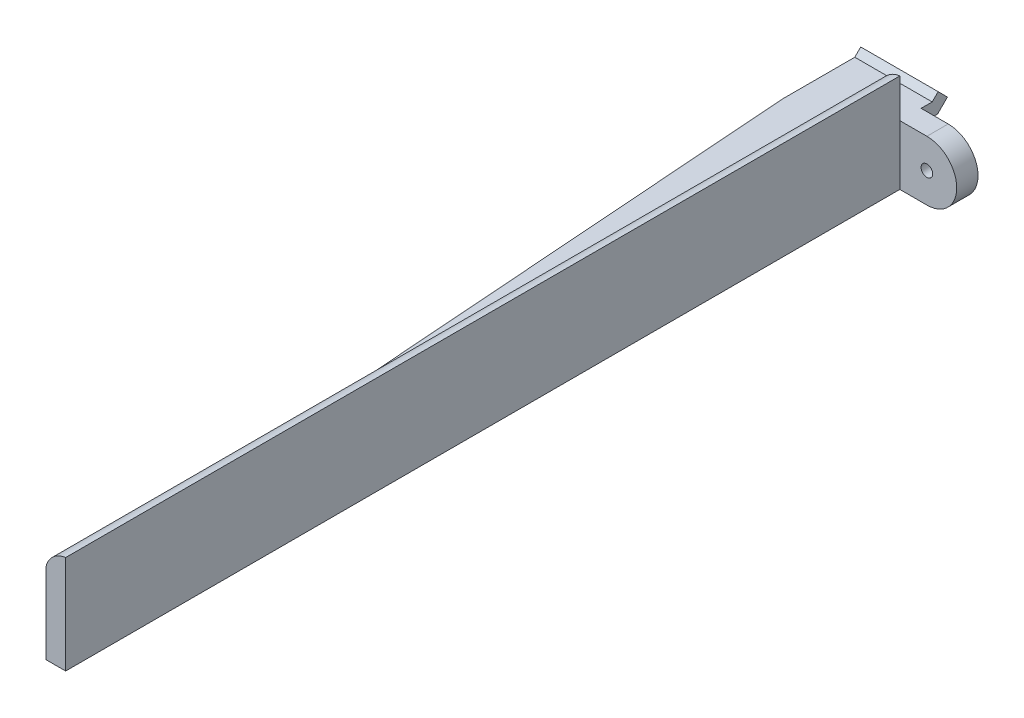
SolidWorks part; units mm, degrees
ref_plane "Front Plane" through (0, 0, 0) normal (0, 0, 1) x (1, 0, 0)
ref_plane "Top Plane" through (0, 0, 0) normal (0, 1, 0) x (1, 0, 0)
ref_plane "Right Plane" through (0, 0, 0) normal (1, 0, 0) x (0, 0, -1)
sketch "Sketch2" plane through (0, 0, 0) normal (0, 0, 1) x (1, 0, 0)
  line L0 (0, 5.9203) -> (0, 8.9503) construction
  line L1 (-5, -5.8182) -> (5, -5.8182)
  line L2 (-5, -5.8182) -> (-5, 8.9503)
  line L3 (-5, 8.9503) -> (5, 8.9503)
  line L4 (5, -5.8182) -> (5, 8.9503)
  line L5 (97.4, 8.9503) -> (117.4, 8.9503) construction
  line L7 (41.5859, 5.9203) -> (-10.4141, 5.9203) construction
  line L8 (0, -5.8182) -> (0, -2.7882) construction
  point P0 (0, 0)
  dimension "D1" = 10
extrude "Boss-Extrude1" add sketch "Sketch2" along normal blind 5
sketch "Sketch8" plane through (-5, 0, 0) normal (-1, 0, 0) x (0, 0, 1)
  line L6 (-0.15, 5.7703) -> (0, 5.7703)
  line L7 (0, 8.9503) -> (0, -5.8182) construction
  line L8 (0, 5.7703) -> (0, 4.0703)
  line L9 (0, 4.0703) -> (-0.15, 4.0703)
  line L11 (-0.15, -1.9297) -> (0, -1.9297)
  line L12 (-2.1379, 4.0703) -> (-0.15, 4.0703)
  line L13 (-0.15, 4.0703) -> (-0.15, 5.7703)
  line L14 (-0.15, 5.7703) -> (-1.4337, 5.7703)
  line L15 (-1.4337, 5.7703) -> (-2.2, 6.5366)
  line L16 (-2.2, 6.5366) -> (-3.4021, 5.3345)
  line L17 (-3.4021, 5.3345) -> (-2.1379, 4.0703)
  line L18 (-2.1379, 4.0703) -> (-0.15, 4.0703)
  line L20 (-0.15, 5.7703) -> (-1.4337, 5.7703)
  line L21 (-1.4337, 5.7703) -> (-2.2, 6.5366)
  line L22 (-2.2, 6.5366) -> (-3.4021, 5.3345)
  line L23 (-3.4021, 5.3345) -> (-2.1379, 4.0703)
  line L24 (-2.1379, -1.9297) -> (-0.15, -1.9297)
  line L25 (-0.15, -1.9297) -> (-0.15, -0.2297)
  line L26 (-0.15, -0.2297) -> (-1.4337, -0.2297)
  line L27 (-1.4337, -0.2297) -> (-2.2, 0.5366)
  line L28 (-2.2, 0.5366) -> (-3.4021, -0.6655)
  line L29 (-3.4021, -0.6655) -> (-2.1379, -1.9297)
  line L30 (-2.1379, -1.9297) -> (-0.15, -1.9297)
  line L32 (-0.15, -0.2297) -> (-1.4337, -0.2297)
  line L33 (-1.4337, -0.2297) -> (-2.2, 0.5366)
  line L34 (-2.2, 0.5366) -> (-3.4021, -0.6655)
  line L35 (-3.4021, -0.6655) -> (-2.1379, -1.9297)
  line L37 (-0.15, -0.2297) -> (0, -0.2297)
  line L38 (0, -1.9297) -> (0, -0.2297)
  dimension "D1" = 0.15
  dimension "D2" = 0.15
extrude "Boss-Extrude4" add sketch "Sketch8" against normal up to surface (10 mm away) up to face at (5, 1.566, 2.5)
sketch "Sketch9" plane through (0, 0, 0) normal (0, 0, -1) x (-1, 0, 0)
  line L4 (-5, 8.9503) -> (-5, 5.7703)
  line L5 (-5, 5.7703) -> (5, 5.7703)
  line L6 (5, 5.7703) -> (5, 8.9503)
  line L7 (5, 8.9503) -> (-5, 8.9503)
  line L8 (-5, 8.9503) -> (-5, 5.7703)
  line L10 (5, 5.7703) -> (5, 8.9503)
  line L11 (5, 8.9503) -> (-5, 8.9503)
  line L16 (5, -1.9297) -> (-5, -1.9297)
  line L17 (-5, -1.9297) -> (-5, -5.8182)
  line L18 (-5, -5.8182) -> (5, -5.8182)
  line L19 (5, -5.8182) -> (5, -1.9297)
  line L21 (-5, -1.9297) -> (-5, -5.8182)
  line L22 (-5, -5.8182) -> (5, -5.8182)
  line L23 (5, -5.8182) -> (5, -1.9297)
  line L26 (-5, 5.7703) -> (5, 5.7703)
  line L27 (5, -1.9297) -> (-5, -1.9297)
  dimension "D1" = 0
  dimension "D2" = 0
extrude "Cut-Extrude3" cut sketch "Sketch9" against normal blind 5
sketch "Sketch10" plane through (0, 5.7703, 0) normal (0, 1, 0) x (1, 0, 0)
  line L0 (-5, -5) -> (-5, -10.5)
  line L1 (-5, -10.5) -> (1.3524, -55.7)
  line L2 (1.3524, -55.7) -> (6.3524, -55.7)
  line L3 (-5, -5) -> (5, -5)
  line L4 (-120.9789, 453.7107) -> (412.3545, 453.7107) construction
  line L5 (6.3524, -55.7) -> (6.3524, -49.2)
  line L6 (5, -5) -> (5, -14)
  arc A1 (5, -14) -> (6.3524, -49.2) centre (39.6089, -30.2962) ccw
  dimension "D1" = 172
  dimension "D2" = 45.2
  dimension "D3" = 5
  dimension "D4" = 6.5
  dimension "D5" = 5.5
  dimension "D6" = 9
extrude "Boss-Extrude5" add sketch "Sketch10" against normal up to surface (7.7 mm away) up to face at (0, -1.9297, 1.4311)
ref_plane "Plane1" through (0, 0, 2.75) normal (0, 0, 1) x (1, 0, 0)
sketch "Sketch12" plane through (0, 0, 0) normal (0, 0, 1) x (1, 0, 0)
  line L0 (5, 5.7703) -> (8.5, 5.7703)
  line L1 (8.5, -1.9297) -> (5, -1.9297)
  line L2 (5, -1.9297) -> (5, 5.7703)
  line L3 (1.3524, 5.7703) -> (6.3524, 5.7703) construction
  line L4 (1.3524, -1.9297) -> (6.3524, -1.9297) construction
  line L5 (5, 5.3345) -> (5, 6.5366) construction
  line L6 (6.3524, 5.7703) -> (1.3552, 5.7703) construction
  arc A0 (8.5, 5.7703) -> (8.5, -1.9297) centre (8.5, 1.9203) cw
  circle A1 centre (8.5, 1.9203) radius 0.75
  dimension "D1" = 1.5
  dimension "D2" = 3.5
extrude "Boss-Extrude7" add sketch "Sketch12" along normal up to surface (2.75 mm away) up to plane "Plane1"
fillet "Fillet1" radius 2.5 4 edges at (6.3524, 1.9203, 55.7) (1.3524, 1.9203, 55.7) (6.3524, 1.9203, 49.2) (5, 1.9203, 14)
sketch "Sketch13" plane through (0, 5.7703, 0) normal (0, 1, 0) x (1, 0, 0)
  line L1 (-5, -10.5) -> (12.8873, -10.5)
  line L2 (-5, -10.5) -> (-5, -56.7292)
  line L3 (-5, -56.7292) -> (12.8873, -56.7292)
  line L4 (12.8873, -10.5) -> (12.8873, -56.7292)
extrude "Cut-Extrude4" cut sketch "Sketch13" against normal blind 20
sketch "Sketch15" plane through (0, 0, 10.5) normal (0, 0, 1) x (1, 0, 0)
  line L1 (-5, 5.7703) -> (5, 5.7703)
  line L2 (-5, 5.7703) -> (-5, -1.9297)
  line L3 (-5, -1.9297) -> (5, -1.9297)
  line L4 (5, 5.7703) -> (5, -1.9297)
extrude "Boss-Extrude9" add sketch "Sketch15" along normal blind 100
sketch "Sketch16" plane through (0, 5.7703, 0) normal (0, 1, 0) x (1, 0, 0)
  line L0 (-5, -7.9528) -> (2.4612, -110.5)
  line L1 (-5, -110.5) -> (-5, 1.4337) construction
  line L2 (5, -110.5) -> (-5, -110.5) construction
  line L3 (2.4612, -110.5) -> (-5, -110.5)
  line L4 (-5, -110.5) -> (-5, -7.9528)
extrude "Cut-Extrude5" cut sketch "Sketch16" against normal blind 100
sketch "Sketch17" plane through (0, 5.7703, 0) normal (0, 1, 0) x (1, 0, 0)
  line L1 (5, -110.5) -> (2.4612, -110.5)
  line L2 (5, -110.5) -> (5, -2.7455)
  line L3 (5, -2.7455) -> (2.4612, -2.7455)
  line L4 (2.4612, -110.5) -> (2.4612, -2.7455)
  point P5 (0, 0)
extrude "Boss-Extrude10" add sketch "Sketch17" along normal blind 5
fillet "Fillet2" radius 3 1 edges at (2.4612, 5.7703, 56.6228)
fillet "Fillet3" radius 3 1 edges at (2.4612, 10.7703, 56.6228)
